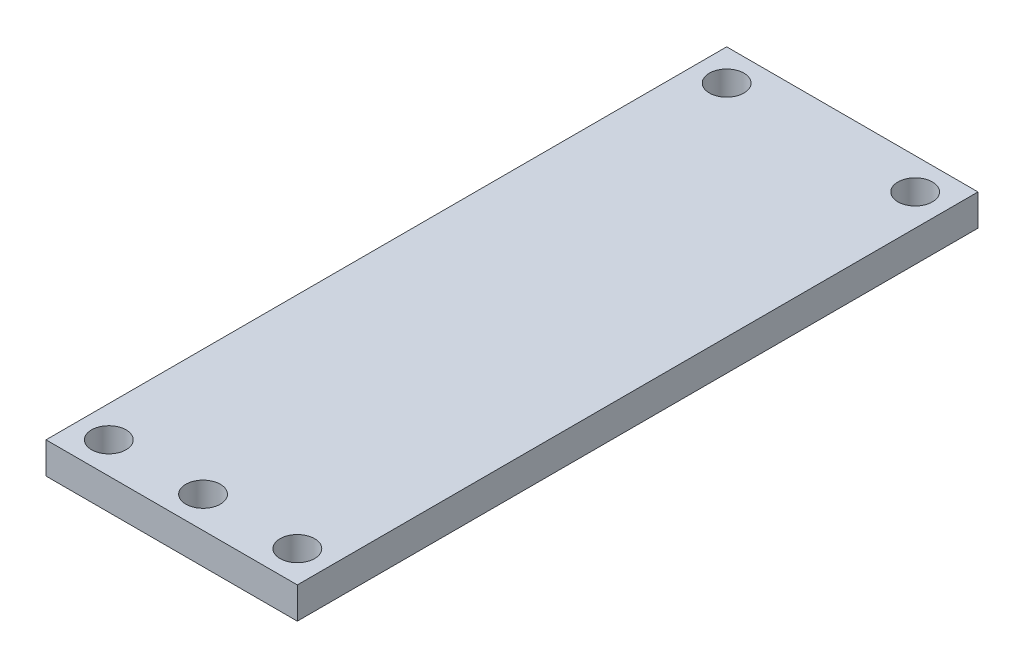
SolidWorks part; units mm, degrees
ref_plane "Front Plane" through (0, 0, 0) normal (0, 0, 1) x (1, 0, 0)
ref_plane "Top Plane" through (0, 0, 0) normal (0, 1, 0) x (1, 0, 0)
ref_plane "Right Plane" through (0, 0, 0) normal (1, 0, 0) x (0, 0, -1)
sketch "Sketch1" plane through (0, 0, 0) normal (0, 1, 0) x (1, 0, 0)
  line L1 (0, 0) -> (24, 0)
  line L2 (0, 0) -> (0, 65)
  line L3 (0, 65) -> (24, 65)
  line L4 (24, 0) -> (24, 65)
  dimension "D1" = 24
  dimension "D2" = 65
extrude "Boss-Extrude1" add sketch "Sketch1" along normal blind 3
sketch "Sketch2" plane through (0, 0, 0) normal (0, 1, 0) x (1, 0, 0)
  line L0 (0, 0) -> (24, 0) construction
  circle A0 centre (3, 3) radius 1.65
  circle A1 centre (12, 3) radius 1.65
  circle A2 centre (21, 3) radius 1.65
  circle A6 centre (3, 62) radius 1.65
  circle A8 centre (21, 62) radius 1.65
  circle A9 centre (12, 32.5) radius 1.65 [skipped]
  circle A10 centre (3, 32.5) radius 1.65 [skipped]
  circle A11 centre (21, 32.5) radius 1.65 [skipped]
  circle A12 centre (12, 62) radius 1.65 [skipped]
  point P9 (12, 0)
  dimension "D1" = 3.3
  dimension "D2" = 3
  dimension "D3" = 9
  dimension "D4" = 9
  dimension "D5" = 3
  dimension "D6" = 59
extrude "Cut-Extrude1" cut sketch "Sketch2" along normal through all
